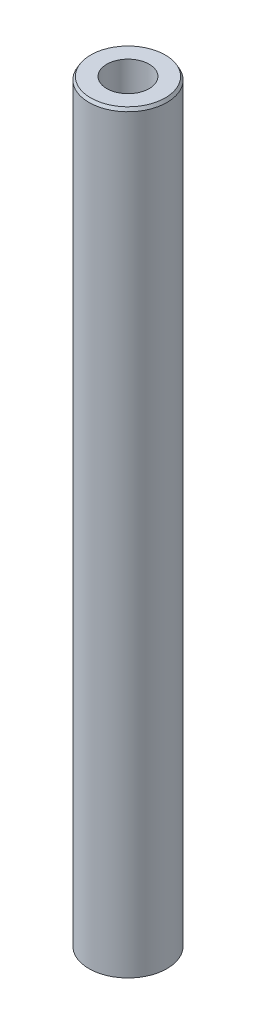
SolidWorks part; units mm, degrees
ref_plane "Front Plane" through (0, 0, 0) normal (0, 0, 1) x (1, 0, 0)
ref_plane "Top Plane" through (0, 0, 0) normal (0, 1, 0) x (1, 0, 0)
ref_plane "Right Plane" through (0, 0, 0) normal (1, 0, 0) x (0, 0, -1)
sketch "Sketch1" plane through (0, 0, 0) normal (0, 1, 0) x (1, 0, 0)
  circle A0 centre (0, 0) radius 12.5
  dimension "SHAFT_OD" = 25
extrude "Boss-Extrude1" add sketch "Sketch1" along normal blind 241.9171
sketch "Sketch2" plane through (0, 0, 0) normal (0, 1, 0) x (1, 0, 0)
  circle A0 centre (0, 0) radius 6.7904
  dimension "BORE_D" = 13.5808
extrude "Cut-Extrude1" cut sketch "Sketch2" along normal through all
chamfer "Chamfer1" distance 0.9797 angle 30 2 edges at (0, 241.9171, 12.5) (0, 0, 12.5) first distance on face at (0, 241.9171, 12.5) first distance on face at (0, 0, 6.7904)
